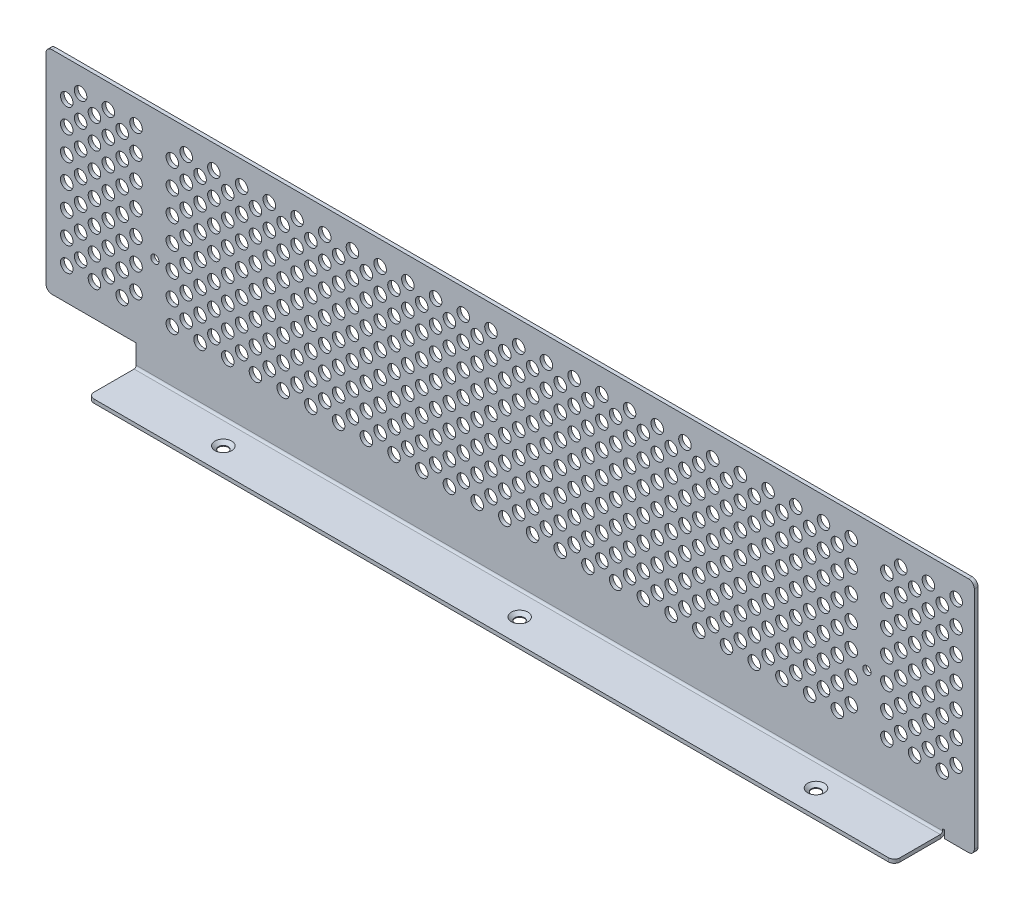
SolidWorks part; units mm, degrees
note: The reader was unsure of these and kept them because the rebuilt part matched: flange length of "Edge-Flange1".
material "6061 Alloy"
ref_plane "Front" through (0, 0, 0) normal (0, 0, 1) x (1, 0, 0)
ref_plane "Top" through (0, 0, 0) normal (0, 1, 0) x (1, 0, 0)
ref_plane "Right" through (0, 0, 0) normal (1, 0, 0) x (0, 0, -1)
sketch "Sketch2" plane through (0, 0, 0) normal (0, 0, 1) x (1, 0, 0)
  line L1 (159.13, 40.64) -> (-159.13, 40.64)
  line L2 (159.13, 40.64) -> (159.13, -40.64)
  line L3 (159.13, -40.64) -> (-128.19, -40.64)
  line L4 (-159.13, 40.64) -> (-159.13, -32)
  line L5 (159.13, 40.64) -> (-128.19, -32.7383) construction
  line L6 (159.13, -40.64) -> (-159.13, 40.64) construction
  line L9 (-159.13, -32) -> (-128.19, -32)
  line L10 (-128.19, -40.64) -> (-128.19, -32)
  point P0 (0, 0)
  dimension "D2" = 81.28
  dimension "D3" = 72.64
  dimension "D4" = 30.94
base flange "Base-Flange1" sketch "Sketch2" thickness 1.27 reverse thickness direction no parameters "D1"=0.7366
edge flange "Edge-Flange1" sketch "Sketch9" flange angle 90 flange length 17.78 flange position material inside bend radius 0.7366 thickness 1.27 parameters "D6"=10
sketch "Sketch9" plane through (0, -40.64, 0) normal (0, -1, 0) x (1, 0, 0)
  line L2 (-128.19, 0) -> (-128.19, 16.51)
  line L3 (-128.19, 16.51) -> (148.21, 16.51)
  line L4 (148.21, 16.51) -> (148.21, 0)
  line L11 (-128.19, 0) -> (159.13, 0) construction
  line L12 (-128.19, 0) -> (148.21, 0)
  dimension "D1" = 276.4
bend "EdgeBend1" bend radius 0.7366 bend angle 90 parameters "D5"=1
hole_wizard "#6 Clearance Hole2" positions "Sketch11" profile "Sketch12" hole size "#6" standard "ANSI Inch" end condition through all
sketch "Sketch11" plane through (0, 0, 0) normal (0, 0, 1) x (1, 0, 0)
  line L0 (-159.13, 40.64) -> (-159.13, -32) construction
  line L1 (159.13, 40.64) -> (-159.13, 40.64) construction
  point P0 (-147.27, 32.51)
  dimension "D1" = 11.86
  dimension "D2" = 8.13
sketch "Sketch12" plane through (-147.27, 32.51, 0) normal (1, 0, 0) x (0, -1, 0)
  line L0 (0, 0) -> (0, 1.27)
  line L1 (0, 1.27) -> (2.1526, 1.27)
  line L2 (2.1526, 1.27) -> (2.1526, 0)
  line L5 (2.1526, 0) -> (0, 0)
  line L11 (0, -6.35) -> (0, 107.95) construction
  dimension "Thru Hole Dia." = 4.3053
  dimension "Thru Hole Depth" = 1.27
pattern_linear "LPattern1" count 3 spacing 9.5 along (1, 0, 0) of "#6 Clearance Hole2"
pattern_linear "LPattern2" count 7 spacing 8.23 along (0, -1, 0) of "LPattern1", "#6 Clearance Hole2"
hole_wizard "#6 Clearance Hole3" positions "Sketch13" profile "Sketch14" hole size "#6" standard "ANSI Inch" end condition through all
sketch "Sketch13" plane through (0, 0, 0) normal (0, 0, 1) x (1, 0, 0)
  line L0 (-159.13, 40.64) -> (-159.13, -32) construction
  line L1 (159.13, 40.64) -> (-159.13, 40.64) construction
  point P0 (-152.02, 28.4)
  dimension "D1" = 7.11
  dimension "D2" = 12.24
sketch "Sketch14" plane through (-152.02, 28.4, 0) normal (1, 0, 0) x (0, -1, 0)
  line L0 (0, 0) -> (0, 1.27)
  line L1 (0, 1.27) -> (2.1526, 1.27)
  line L2 (2.1526, 1.27) -> (2.1526, 0)
  line L5 (2.1526, 0) -> (0, 0)
  line L11 (0, -6.35) -> (0, 107.95) construction
  dimension "Thru Hole Dia." = 4.3053
  dimension "Thru Hole Depth" = 1.27
pattern_linear "LPattern3" count 3 spacing 9.5 along (1, 0, 0) of "#6 Clearance Hole3"
pattern_linear "LPattern4" count 7 spacing 8.23 along (0, -1, 0) of "LPattern3", "#6 Clearance Hole3"
hole_wizard "#6 Clearance Hole4" positions "Sketch15" profile "Sketch16" hole size "#6" standard "ANSI Inch" end condition through all
sketch "Sketch15" plane through (0, 0, 0) normal (0, 0, 1) x (1, 0, 0)
  line L0 (159.13, 40.64) -> (-159.13, 40.64) construction
  circle A0 centre (-128.27, 32.51) radius 2.1527 construction
  circle A1 centre (-133.02, 28.4) radius 2.1527 construction
  point P0 (-111.07, 32.51)
  point P12 (-115.82, 28.4)
  dimension "D1" = 17.2
  dimension "D3" = 17.2
  dimension "D2" = 8.13
  dimension "D4" = 12.24
sketch "Sketch16" plane through (-111.07, 32.51, 0) normal (1, 0, 0) x (0, -1, 0)
  line L0 (0, 0) -> (0, 1.27)
  line L1 (0, 1.27) -> (2.1526, 1.27)
  line L2 (2.1526, 1.27) -> (2.1526, 0)
  line L5 (2.1526, 0) -> (0, 0)
  line L11 (0, -6.35) -> (0, 107.95) construction
  dimension "Thru Hole Dia." = 4.3053
  dimension "Thru Hole Depth" = 1.27
pattern_linear "LPattern5" count 7 spacing 8.23 along (0, -1, 0) of "#6 Clearance Hole4"
pattern_linear "LPattern6" count 25 spacing 9.5 along (1, 0, 0) of "LPattern5", "#6 Clearance Hole4"
pattern_linear "LPattern7" count 2 spacing 281.18 along (1, 0, 0) of "LPattern2", "LPattern4", "#6 Clearance Hole2", "LPattern1", "#6 Clearance Hole3", "LPattern3"
hole_wizard "#34 (0.111) Diameter Hole4" positions "Sketch17" profile "Sketch18" hole size "#34" standard "ANSI Inch" end condition through all
sketch "Sketch17" plane through (0, 0, 0) normal (0, 0, 1) x (1, 0, 0)
  line L0 (-159.13, 40.64) -> (-159.13, -32) construction
  line L1 (159.13, 40.64) -> (-159.13, 40.64) construction
  point P0 (-121.79, -3.96)
  dimension "D1" = 37.34
  dimension "D2" = 44.6
sketch "Sketch18" plane through (-121.79, -3.96, 0) normal (1, 0, 0) x (0, -1, 0)
  line L0 (0, 0) -> (0, 1.27)
  line L1 (0, 1.27) -> (1.4097, 1.27)
  line L2 (1.4097, 1.27) -> (1.4097, 0)
  line L5 (1.4097, 0) -> (0, 0)
  line L11 (0, -6.35) -> (0, 107.95) construction
  dimension "Thru Hole Dia." = 2.8194
  dimension "Thru Hole Depth" = 1.27
pattern_linear "LPattern8" count 2 spacing 244.11 along (1, 0, 0) of "#34 (0.111) Diameter Hole4"
hole_wizard "CSK for #4 Flat Head Machine Screw (100)1" positions "Sketch19" profile "Sketch20" countersink size "#4" standard "ANSI Inch" end condition through all
sketch "Sketch19" plane through (0, -39.37, 0) normal (0, 1, 0) x (1, 0, 0)
  line L0 (148.21, -16.51) -> (-128.19, -16.51) construction
  line L1 (-128.19, -16.51) -> (-128.19, -0.7366) construction
  point P0 (-90.09, -8.25)
  point P7 (11.51, -8.25)
  point P9 (113.11, -8.25)
  dimension "D1" = 8.26
  dimension "D2" = 38.1
  dimension "D3" = 101.6
  dimension "D4" = 101.6
sketch "Sketch20" plane through (-90.09, -39.37, 8.25) normal (1, 0, 0) x (0, 0, 1)
  line L0 (0, 0) -> (0, 1.27)
  line L1 (0, 1.27) -> (1.6319, 1.27)
  line L2 (1.6319, 1.27) -> (1.6319, 1.0284)
  line L3 (1.6319, 1.0284) -> (2.8575, 0)
  line L5 (2.8575, 0) -> (0, 0)
  line L6 (-1.632, 1.0284) -> (-2.8575, 0) construction
  line L11 (0, -6.35) -> (0, 107.95) construction
  dimension "Thru Hole Dia." = 3.2639
  dimension "Thru Hole Depth" = 1.27
  dimension "Near C'Sink Dia." = 5.715
  dimension "Near C'Sink Angle" = 100
fillet "Fillet1" radius 2 6 edges at (-159.13, 40.64, -0.635) (-159.13, -32, -0.635) (-128.19, -40.005, 16.51) (148.21, -40.005, 16.51) (159.13, 40.64, -0.635) (159.13, -40.64, -0.635)
sketch "Bend-Lines1" [suppressed] plane through (0, 0, 0) normal (0, 1, 0) x (1, 0, 0)
sketch "Bounding-Box1" [suppressed] plane through (0, 0, 0) normal (0, 1, 0) x (1, 0, 0)
sheet metal parameters "Sheet-Metal2" thickness 1.27 parameters "D1"=0.7366
flat pattern "Flat-Pattern2" [suppressed]
sketch "Bend-Lines2" plane through (0, 0, 0) normal (0, 1, 0) x (1, 0, 0)
sketch "Bounding-Box2" [suppressed] plane through (0, 0, 0) normal (0, 1, 0) x (1, 0, 0)
sheet metal parameters "Sheet-Metal3" thickness 1.27 parameters "D1"=0.7366
flat pattern "Flat-Pattern2" [suppressed]
sketch "Bend-Lines2" plane through (0, 0, 0) normal (0, 1, 0) x (1, 0, 0)
sketch "Bounding-Box2" [suppressed] plane through (0, 0, 0) normal (0, 1, 0) x (1, 0, 0)
bend of the flat pattern "Flatten-<EdgeBend1>1"
sheet metal parameters "Sheet-Metal4" thickness 1.27 parameters "D1"=0.7366
flat pattern "Flat-Pattern2" [suppressed]
sketch "Bend-Lines2" plane through (0, 0, 0) normal (0, 1, 0) x (1, 0, 0)
sketch "Bounding-Box2" [suppressed] plane through (0, 0, 0) normal (0, 1, 0) x (1, 0, 0)
bend of the flat pattern "Flatten-<EdgeBend1>1"
sheet metal parameters "Sheet-Metal5" thickness 1.27 parameters "D1"=0.7366
flat pattern "Flat-Pattern2" [suppressed]
sketch "Bend-Lines2" plane through (0, 0, 0) normal (0, 1, 0) x (1, 0, 0)
sketch "Bounding-Box2" [suppressed] plane through (0, 0, 0) normal (0, 1, 0) x (1, 0, 0)
bend of the flat pattern "Flatten-<EdgeBend1>1"
sheet metal parameters "Sheet-Metal6" thickness 1.27 parameters "D1"=0.7366
flat pattern "Flat-Pattern2" [suppressed]
sketch "Bend-Lines2" plane through (0, 0, 0) normal (0, 1, 0) x (1, 0, 0)
sketch "Bounding-Box2" [suppressed] plane through (0, 0, 0) normal (0, 1, 0) x (1, 0, 0)
bend of the flat pattern "Flatten-<EdgeBend1>1"
sheet metal parameters "Sheet-Metal7" thickness 1.27 parameters "D1"=0.7366
flat pattern "Flat-Pattern2" [suppressed]
sketch "Bend-Lines2" plane through (0, 0, 0) normal (0, 1, 0) x (1, 0, 0)
sketch "Bounding-Box2" [suppressed] plane through (0, 0, 0) normal (0, 1, 0) x (1, 0, 0)
bend of the flat pattern "Flatten-<EdgeBend1>1"
sheet metal parameters "Sheet-Metal8" thickness 1.27 parameters "D1"=0.7366
flat pattern "Flat-Pattern2" [suppressed]
sketch "Bend-Lines2" plane through (0, 0, 0) normal (0, 1, 0) x (1, 0, 0)
sketch "Bounding-Box2" [suppressed] plane through (0, 0, 0) normal (0, 1, 0) x (1, 0, 0)
bend of the flat pattern "Flatten-<EdgeBend1>1"
sheet metal parameters "Sheet-Metal9" thickness 1.27 parameters "D1"=0.7366
flat pattern "Flat-Pattern2" [suppressed]
sketch "Bend-Lines2" plane through (0, 0, 0) normal (0, 1, 0) x (1, 0, 0)
sketch "Bounding-Box2" [suppressed] plane through (0, 0, 0) normal (0, 1, 0) x (1, 0, 0)
bend of the flat pattern "Flatten-<EdgeBend1>1"
sheet metal parameters "Sheet-Metal10" thickness 1.27 parameters "D1"=0.7366
flat pattern "Flat-Pattern2" [suppressed]
sketch "Bend-Lines2" plane through (0, 0, 0) normal (0, 1, 0) x (1, 0, 0)
sketch "Bounding-Box2" [suppressed] plane through (0, 0, 0) normal (0, 1, 0) x (1, 0, 0)
bend of the flat pattern "Flatten-<EdgeBend1>1"
sheet metal parameters "Sheet-Metal11" thickness 1.27 parameters "D1"=0.7366
flat pattern "Flat-Pattern2" [suppressed]
sketch "Bend-Lines2" plane through (0, 0, 0) normal (0, 1, 0) x (1, 0, 0)
sketch "Bounding-Box2" [suppressed] plane through (0, 0, 0) normal (0, 1, 0) x (1, 0, 0)
bend of the flat pattern "Flatten-<EdgeBend1>1"
sheet metal parameters "Sheet-Metal12" thickness 1.27 parameters "D1"=0.7366
flat pattern "Flat-Pattern2" [suppressed]
sketch "Bend-Lines2" plane through (0, 0, 0) normal (0, 1, 0) x (1, 0, 0)
sketch "Bounding-Box2" [suppressed] plane through (0, 0, 0) normal (0, 1, 0) x (1, 0, 0)
bend of the flat pattern "Flatten-<EdgeBend1>1"
sheet metal parameters "Sheet-Metal13" thickness 1.27 parameters "D1"=0.7366
flat pattern "Flat-Pattern2" [suppressed]
sketch "Bend-Lines2" plane through (0, 0, 0) normal (0, 1, 0) x (1, 0, 0)
sketch "Bounding-Box2" [suppressed] plane through (0, 0, 0) normal (0, 1, 0) x (1, 0, 0)
bend of the flat pattern "Flatten-<EdgeBend1>1"
sheet metal parameters "Sheet-Metal14" thickness 1.27 parameters "D1"=0.7366
flat pattern "Flat-Pattern2" [suppressed]
sketch "Bend-Lines2" plane through (0, 0, 0) normal (0, 1, 0) x (1, 0, 0)
sketch "Bounding-Box2" [suppressed] plane through (0, 0, 0) normal (0, 1, 0) x (1, 0, 0)
bend of the flat pattern "Flatten-<EdgeBend1>1"
sheet metal parameters "Sheet-Metal15" thickness 1.27 parameters "D1"=0.7366
flat pattern "Flat-Pattern2" [suppressed]
sketch "Bend-Lines2" plane through (0, 0, 0) normal (0, 1, 0) x (1, 0, 0)
sketch "Bounding-Box2" [suppressed] plane through (0, 0, 0) normal (0, 1, 0) x (1, 0, 0)
bend of the flat pattern "Flatten-<EdgeBend1>1"
sheet metal parameters "Sheet-Metal16" thickness 1.27 parameters "D1"=0.7366
flat pattern "Flat-Pattern2"
sketch "Bend-Lines2" plane through (0, 0, 0) normal (0, 0, 1) x (1, 0, 0)
  line L0 (-128.19, -39.7107) -> (148.21, -39.7107) construction
  line L1 (-128.19, -39.7107) -> (148.21, -39.7107) construction
sketch3d "Bounding-Box2" [suppressed]
  line L0 (159.13, -56.5613, -1.27) -> (-159.13, -56.5613, -1.27) construction
  line L1 (159.13, 40.64, -1.27) -> (-159.13, 40.64, -1.27) construction
  line L2 (159.13, -56.5613, -1.27) -> (159.13, 40.64, -1.27) construction
  line L3 (-159.13, -56.5613, -1.27) -> (-159.13, 40.64, -1.27) construction
bend of the flat pattern "Flatten-<EdgeBend1>1"
